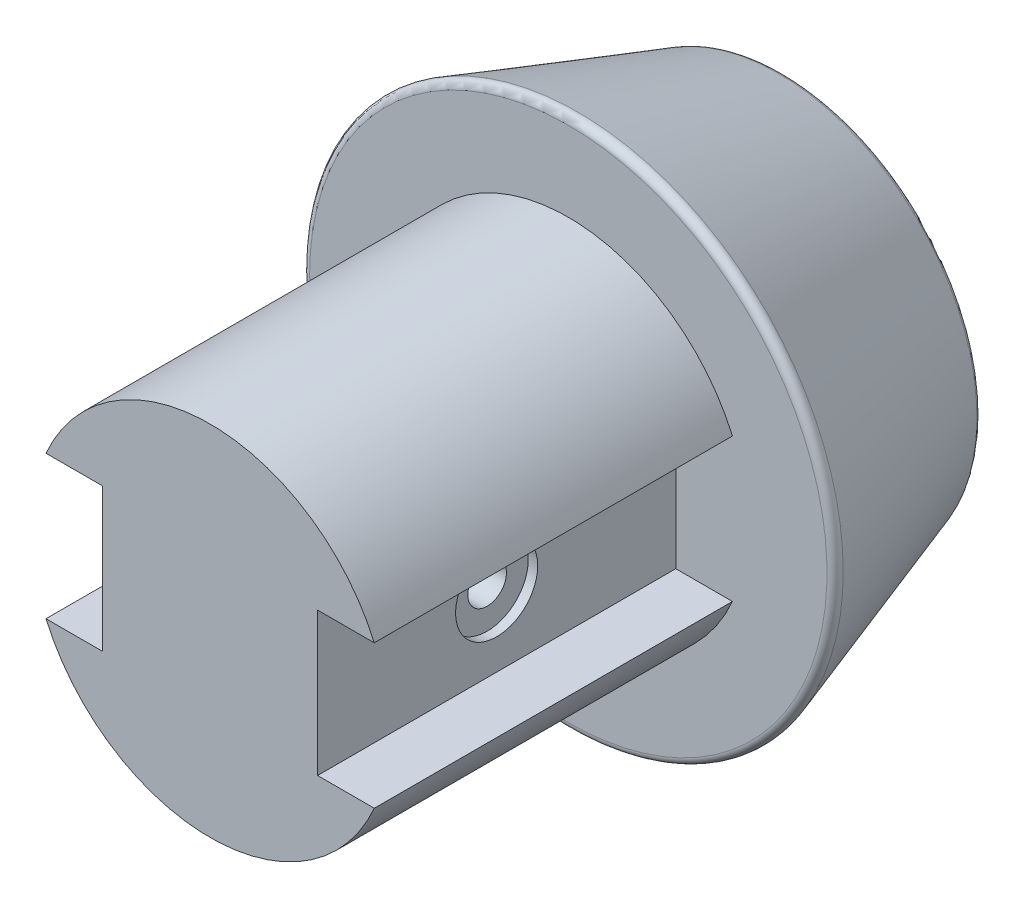
SolidWorks part; units mm, degrees
ref_plane "Front Plane" through (0, 0, 0) normal (0, 0, 1) x (1, 0, 0)
ref_plane "Top Plane" through (0, 0, 0) normal (0, 1, 0) x (1, 0, 0)
ref_plane "Right Plane" through (0, 0, 0) normal (1, 0, 0) x (0, 0, -1)
other "Configuration Table"
sketch "Sketch1" plane through (0, 0, 0) normal (0, 0, 1) x (1, 0, 0)
  line L1 (-5.8199, 2.54) -> (-3.81, 2.54)
  line L2 (-5.8199, 2.54) -> (-5.8199, -2.54)
  line L3 (-5.8199, -2.54) -> (-3.81, -2.54)
  line L4 (-3.81, 2.54) -> (-3.81, -2.54)
  line L5 (-5.8199, 2.54) -> (-3.81, -2.54) construction
  line L6 (-5.8199, -2.54) -> (-3.81, 2.54) construction
  line L7 (3.81, 2.54) -> (5.8199, 2.54)
  line L8 (3.81, 2.54) -> (3.81, -2.54)
  line L9 (3.81, -2.54) -> (5.8199, -2.54)
  line L10 (5.8199, 2.54) -> (5.8199, -2.54)
  line L11 (3.81, 2.54) -> (5.8199, -2.54) construction
  line L12 (3.81, -2.54) -> (5.8199, 2.54) construction
  circle A0 centre (0, 0) radius 6.35
  point P7 (-4.8149, 0)
  point P12 (4.8149, 0)
  dimension "D1" = 12.7
  dimension "D2" = 7.62
  dimension "D3" = 5.08
extrude "Boss-Extrude1" add sketch "Sketch1" along normal blind 12.7 contours L7 A0 L1 L4 L3 L9 L8 region at (0, 0, 0)
sketch "Sketch2" plane through (0, 0, 0) normal (0, 0, -1) x (-1, 0, 0)
  circle A0 centre (0, 0) radius 9.525
  dimension "D1" = 19.05
ref_plane "Plane1" through (0, 0, -7.62) normal (0, 0, 1) x (1, 0, 0)
sketch "Sketch3" plane through (0, 0, -7.62) normal (0, 0, 1) x (1, 0, 0)
  circle A0 centre (0, 0) radius 6.985
  dimension "D1" = 13.97
loft "Loft1" add profiles "Sketch2", "Sketch3" connector at (-0.3797, 9.5174, 0) connector at (-0.386, 6.9743, -7.62)
fillet "Fillet1" radius 0.254 2 edges at (-9.525, 0, 0) (6.985, 0, -7.62)
sketch "Sketch4" plane through (0, 0, 0) normal (0, 1, 0) x (1, 0, 0)
  line L0 (-5.8199, -12.7) -> (5.8199, -12.7) construction
  circle A0 centre (0, -6.35) radius 2.286
  point P2 (0, -12.7)
  dimension "D1" = 4.572
  dimension "D2" = 6.35
extrude "Cut-Extrude1" cut sketch "Sketch4" against normal through all and the other way blind 2.54
scale "Scale1" scale about centroid uniform scaling yes scale factor 1.5
hole_wizard "CBORE for #1 Pan Head Machine Screw2" positions "Sketch8" profile "Sketch7" counterbore size "#1" standard "ANSI Inch" end condition through all
sketch "Sketch8" plane through (5.715, 0, 0) normal (1, 0, 0) x (0, 0, -1)
  line L0 (-18.7401, -3.8577) -> (0.3099, 3.7623) construction
  point P0 (-9.2151, -0.0477)
sketch "Sketch7" plane through (5.715, -0.0477, 9.2151) normal (0, 1, 0) x (0, 0, -1)
  line L0 (0, 0) -> (0, 19.8549)
  line L1 (0, 19.8549) -> (1.0287, 19.8549)
  line L3 (1.0287, 19.8549) -> (1.0287, 0.508)
  line L4 (1.0287, 0.508) -> (2.1831, 0.508)
  line L5 (2.1831, 0.508) -> (2.1831, 0)
  line L7 (2.1831, 0) -> (0, 0)
  line L11 (0, -6.35) -> (0, 107.95) construction
  dimension "Thru Hole Dia." = 2.0574
  dimension "Thru Hole Depth" = 19.8549
  dimension "C'Bore Dia." = 4.3663
  dimension "C'Bore Depth" = 0.508
mirror "Mirror1" about plane through (0, 0, 0) normal (1, 0, 0) of "CBORE for #1 Pan Head Machine Screw2"
